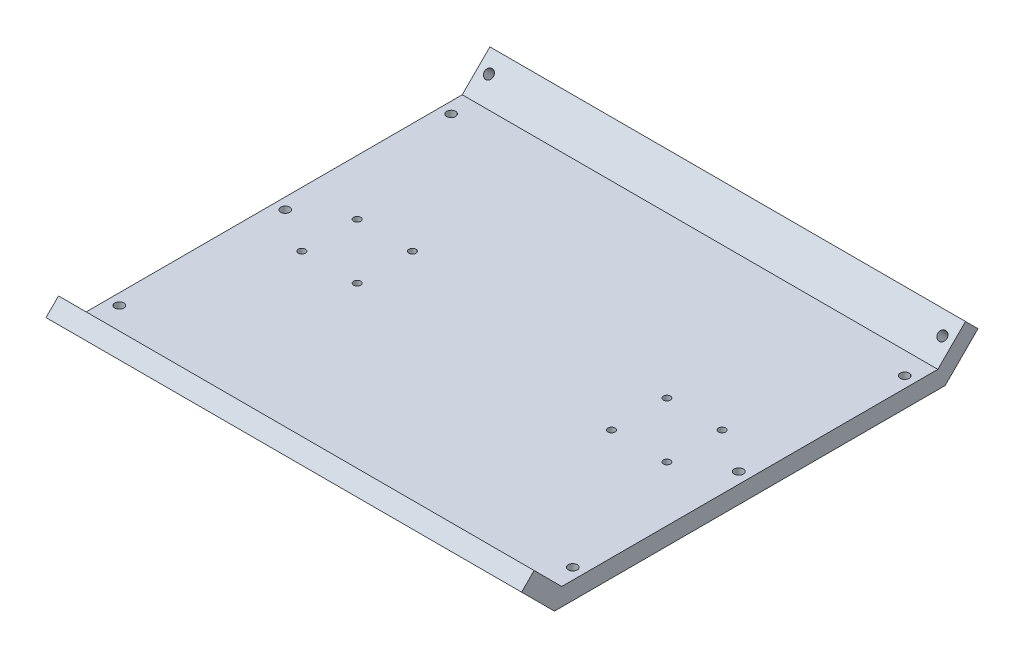
SolidWorks part; units mm, degrees
material "ABS"
ref_plane "Front Plane" through (0, 0, 0) normal (0, 0, 1) x (1, 0, 0)
ref_plane "Top Plane" through (0, 0, 0) normal (0, 1, 0) x (1, 0, 0)
ref_plane "Right Plane" through (0, 0, 0) normal (1, 0, 0) x (0, 0, -1)
sketch "Sketch2" plane through (0, 0, 0) normal (1, 0, 0) x (0, 0, -1)
  line L0 (-85, 0) -> (85, 0)
  line L1 (85, 0) -> (97.5, 12.5)
  line L2 (-85, 0) -> (-97.5, 12.5)
  line L8 (-88.3137, -8) -> (-103.1569, 6.8431)
  line L9 (-88.3137, -8) -> (88.3137, -8)
  line L10 (88.3137, -8) -> (103.1569, 6.8431)
  line L11 (-103.1569, 6.8431) -> (-97.5, 12.5)
  line L12 (97.5, 12.5) -> (103.1569, 6.8431)
  line L13 (97.5, 12.5) -> (110, 25) construction
  line L14 (-97.5, 12.5) -> (-110, 25) construction
  point P4 (0, 0)
  dimension "D2" = 135
  dimension "D3" = 135
  dimension "D1" = 220
  dimension "D4" = 25
  dimension "D5" = 8
extrude "Main" add sketch "Sketch2" along normal mid plane 215
hole_wizard "Ø4.0mm Dowel Hole1" positions "3DSketch1" profile "Sketch3" hole size "Ø4.0" standard "ANSI Metric" end condition through all
sketch3d "3DSketch1"
  line L0 (-107.5, 7.0711, -92.0711) -> (-102.5, 7.0711, -92.0711) construction
  line L1 (-107.5, 12.5, -97.5) -> (-107.5, 0, -85) construction
  line L2 (-102.5, 7.0711, -92.0711) -> (-102.5, 0, -85) construction
  line L3 (107.5, 0, -85) -> (-107.5, 0, -85) construction
  line L4 (-102.5, 0, -85) -> (-102.5, 0, -75) construction
  line L5 (-102.5, 0, -75) -> (-102.5, 0, 0) construction
  line L6 (-102.5, 0, 0) -> (-102.5, 0, 75) construction
  line L7 (-102.5, 0, 75) -> (-102.5, 0, 85) construction
  line L8 (107.5, 0, 85) -> (-107.5, 0, 85) construction
  line L13 (-102.5, 0, 85) -> (-102.5, 7.0711, 92.0711) construction
  line L14 (-102.5, 7.0711, 92.0711) -> (-107.5, 7.0711, 92.0711) construction
  line L15 (-107.5, 0, 85) -> (-107.5, 12.5, 97.5) construction
  line L20 (102.5, 0, -85) -> (102.5, 0, -75) construction
  line L21 (102.5, 0, -75) -> (102.5, 0, 0) construction
  line L22 (102.5, 0, 0) -> (102.5, 0, 75) construction
  line L23 (102.5, 0, 75) -> (102.5, 0, 85) construction
  line L24 (102.5, 0, 85) -> (102.5, 7.0711, 92.0711) construction
  line L25 (102.5, 7.0711, 92.0711) -> (107.5, 7.0711, 92.0711) construction
  line L26 (107.5, 0, 85) -> (107.5, 12.5, 97.5) construction
  line L28 (102.5, 0, -85) -> (102.5, 7.0711, -92.0711) construction
  line L29 (102.5, 7.0711, -92.0711) -> (107.5, 7.0711, -92.0711) construction
  line L30 (107.5, 12.5, -97.5) -> (107.5, 0, -85) construction
  line L32 (107.5, 0, 85) -> (102.5, 0, 85) construction
  line L34 (-102.5, 0, 85) -> (-107.5, 0, 85) construction
  point P0 (-102.5, 7.0711, -92.0711)
  point P2 (-102.5, 0, -75)
  point P4 (-102.5, 0, 0)
  point P6 (-102.5, 0, 75)
  point P8 (-102.5, 7.0711, 92.0711)
  point P10 (102.5, 7.0711, 92.0711)
  point P12 (102.5, 0, 75)
  point P14 (102.5, 0, 0)
  point P16 (102.5, 0, -75)
  point P18 (102.5, 7.0711, -92.0711)
  dimension "D1" = 5
  dimension "D2" = 10
  dimension "D3" = 10
sketch "Sketch3" plane through (-102.5, 7.0711, -92.0711) normal (1, 0, 0) x (0, -0.7071, 0.7071)
  line L0 (0, 0) -> (0, 18.4957)
  line L1 (0, 18.4957) -> (2.05, 18.4957)
  line L2 (2.05, 18.4957) -> (2.05, 0)
  line L5 (2.05, 0) -> (0, 0)
  line L11 (0, -6.35) -> (0, 107.95) construction
  dimension "Thru Hole Dia." = 4.1
  dimension "Thru Hole Depth" = 18.4957
sketch "Sketch4" plane through (0, -8, 0) normal (0, -1, 0) x (1, 0, 0)
  line L1 (57.5, 12.5) -> (82.5, 12.5) construction
  line L2 (57.5, 12.5) -> (57.5, -12.5) construction
  line L3 (57.5, -12.5) -> (82.5, -12.5) construction
  line L4 (82.5, 12.5) -> (82.5, -12.5) construction
  line L5 (57.5, 12.5) -> (82.5, -12.5) construction
  line L6 (57.5, -12.5) -> (82.5, 12.5) construction
  circle A0 centre (57.5, 12.5) radius 1.6
  circle A1 centre (82.5, 12.5) radius 1.6
  circle A2 centre (82.5, -12.5) radius 1.6
  circle A3 centre (57.5, -12.5) radius 1.6
  point P0 (70, 0)
  dimension "D1" = 3.2
  dimension "D2" = 25
  dimension "D3" = 25
  dimension "D4" = 70
extrude "Attachment screw holes" cut sketch "Sketch4" against normal through all
mirror "Mirror1" about plane through (0, 0, 0) normal (1, 0, 0) of "Attachment screw holes"
equation "\"length\" = 215mm"
equation "\"D1@Main\" = \"length\""
equation "\"width\" = 220mm"
equation "\"height\" = 100mm"
equation "\"skin_th\" = 8mm"
equation "\"D1@Sketch2\"=\"width\""
equation "\"D5@Sketch2\"=\"skin_th\""
